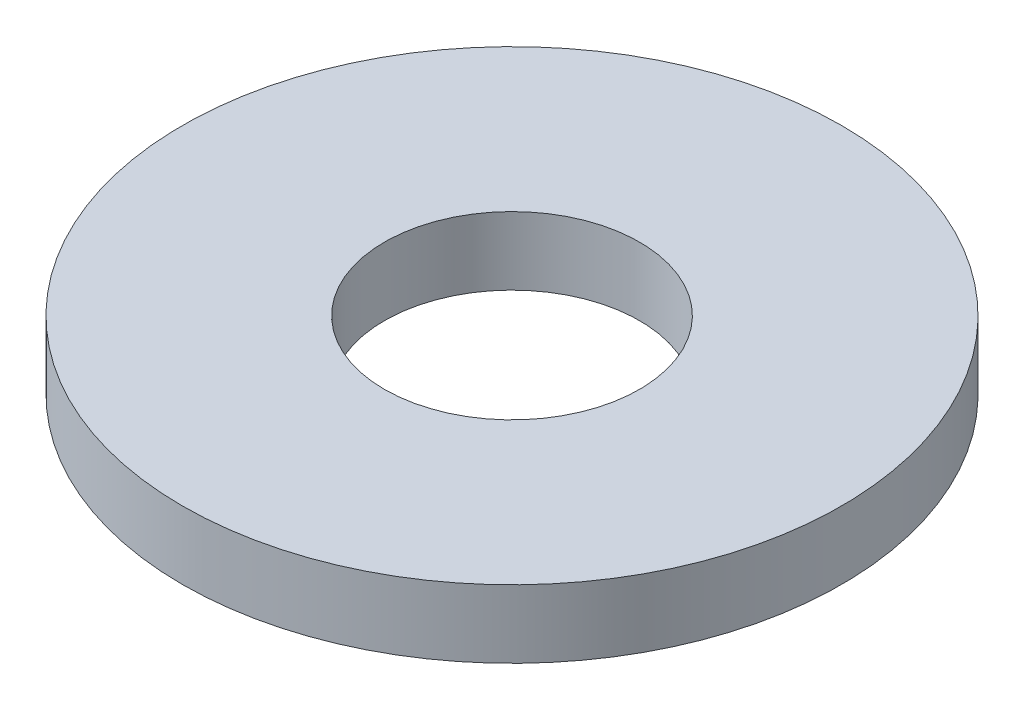
SolidWorks part; units mm, degrees
ref_plane "Front Plane" through (0, 0, 0) normal (0, 0, 1) x (1, 0, 0)
ref_plane "Top Plane" through (0, 0, 0) normal (0, 1, 0) x (1, 0, 0)
ref_plane "Right Plane" through (0, 0, 0) normal (1, 0, 0) x (0, 0, -1)
sketch "Sketch1" plane through (0, 0, 0) normal (0, 1, 0) x (1, 0, 0)
  circle A0 centre (0, 0) radius 77.5
  dimension "FLANGE_OD" = 155
extrude "Boss-Extrude1" add sketch "Sketch1" along normal blind 16
sketch "Sketch2" plane through (0, 0, 0) normal (0, 1, 0) x (1, 0, 0)
  circle A0 centre (0, 0) radius 30
  dimension "BORE_D" = 60
extrude "Cut-Extrude1" cut sketch "Sketch2" along normal through all
sketch "Sketch3" plane through (0, 16, 0) normal (0, 1, 0) x (1, 0, 0)
  circle A0 centre (0, 0) radius 19.6717 construction
  circle A1 centre (-19.6717, 0) radius 6.8667
  dimension "BOLT_D" = 13.7334
  dimension "BOLT_PCD" = 39.3434
extrude "Cut-Extrude2" cut sketch "Sketch3" against normal blind 13.7509 rebuild error yes
pattern_circular "CirPattern1" count 6 over 360 rebuild error yes
